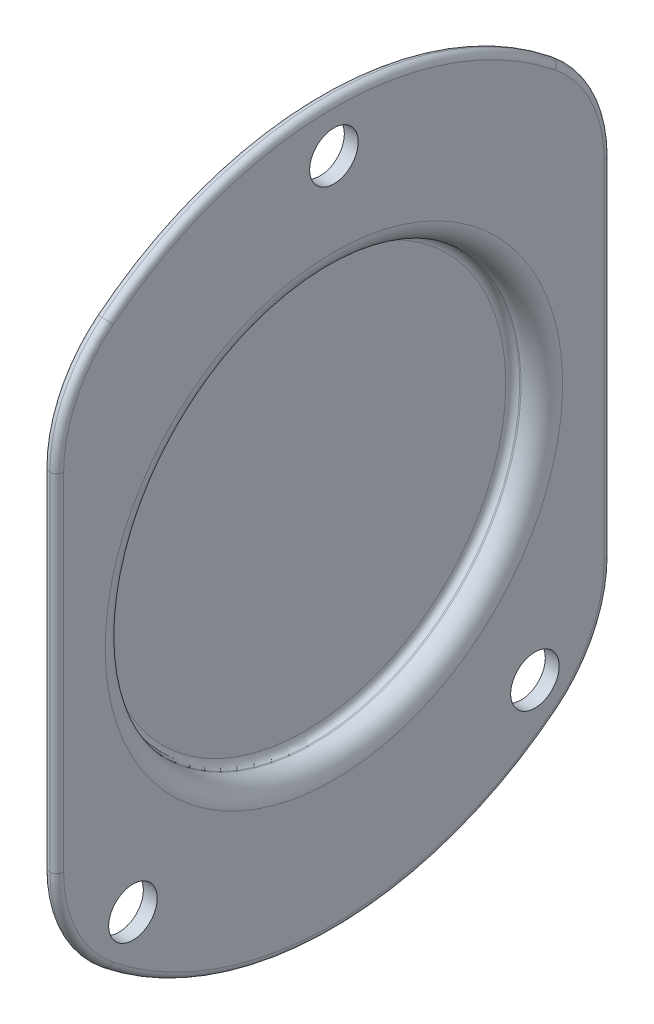
SolidWorks part; units mm, degrees
ref_plane "Front Plane" through (0, 0, 0) normal (0, 0, 1) x (1, 0, 0)
ref_plane "Top Plane" through (0, 0, 0) normal (0, 1, 0) x (1, 0, 0)
ref_plane "Right Plane" through (0, 0, 0) normal (1, 0, 0) x (0, 0, -1)
sketch "Sketch1" plane through (0, 0, 0) normal (0, 0, 1) x (1, 0, 0)
  line L0 (0, 0) -> (0, 29)
  line L1 (1, 30) -> (1.2, 30)
  line L2 (4.2, 33) -> (4.2, 52)
  line L3 (4.2, 52) -> (2.2, 52)
  line L4 (2.2, 52) -> (2.2, 33)
  line L5 (1.2, 32) -> (1, 32)
  line L6 (-2, 29) -> (-2, 0)
  line L7 (-2, 0) -> (0, 0)
  arc A0 (0, 29) -> (1, 30) centre (1, 29) cw
  arc A1 (2.2, 33) -> (1.2, 32) centre (1.2, 33) cw
  arc A2 (1.2, 30) -> (4.2, 33) centre (1.2, 33) ccw
  arc A3 (1, 32) -> (-2, 29) centre (1, 29) ccw
  point P15 (4.2, 30)
  dimension "D7" = 1
  dimension "D8" = 3
  dimension "D1" = 30
  dimension "D2" = 2
  dimension "D3" = 2
  dimension "D4" = 2
  dimension "D5" = 4.2
  dimension "D6" = 52
revolve "Revolve1" add sketch "Sketch1" angle 360 about L7
sketch "Sketch2" plane through (4.2, 0, 0) normal (1, 0, 0) x (0, 0, -1)
  line L1 (-40, 52) -> (40, 52)
  line L2 (-40, 52) -> (-40, -52)
  line L3 (-40, -52) -> (40, -52)
  line L4 (40, 52) -> (40, -52)
  point P4 (-40, 0)
  point P5 (0, -52)
  dimension "D1" = 104
  dimension "D2" = 80
extrude "Cut-Extrude1" cut sketch "Sketch2" against normal through all flip side to cut
sketch "Sketch3" plane through (4.2, 0, 0) normal (1, 0, 0) x (0, 0, -1)
  circle A0 centre (0, 45) radius 3.5
  circle A1 centre (-29, -35) radius 3.5
  circle A2 centre (29, -35) radius 3.5
  dimension "D4" = 7
  dimension "D1" = 35
  dimension "D2" = 29
  dimension "D3" = 29
  dimension "D5" = 45
extrude "Cut-Extrude2" cut sketch "Sketch3" against normal blind 10
fillet "Fillet1" radius 20 4 edges at (3.2, -33.2265, -40) (3.2, 33.2265, -40) (3.2, -33.2265, 40) (3.2, 33.2265, 40)
fillet "Fillet2" radius 1 16 edges at (2.2, 33.6402, 38.0278) (2.2, 0, 40) (2.2, -33.6402, 38.0278) (2.2, -52, 0) (2.2, -33.6402, -38.0278) (2.2, 0, -40) (2.2, 33.6402, -38.0278) (4.2, 33.6402, 38.0278) (4.2, 0, 40) (4.2, -33.6402, 38.0278) (4.2, -52, 0) (4.2, -33.6402, -38.0278) (4.2, 0, -40) (4.2, 33.6402, -38.0278) (2.2, 52, 0) (4.2, 52, 0)
